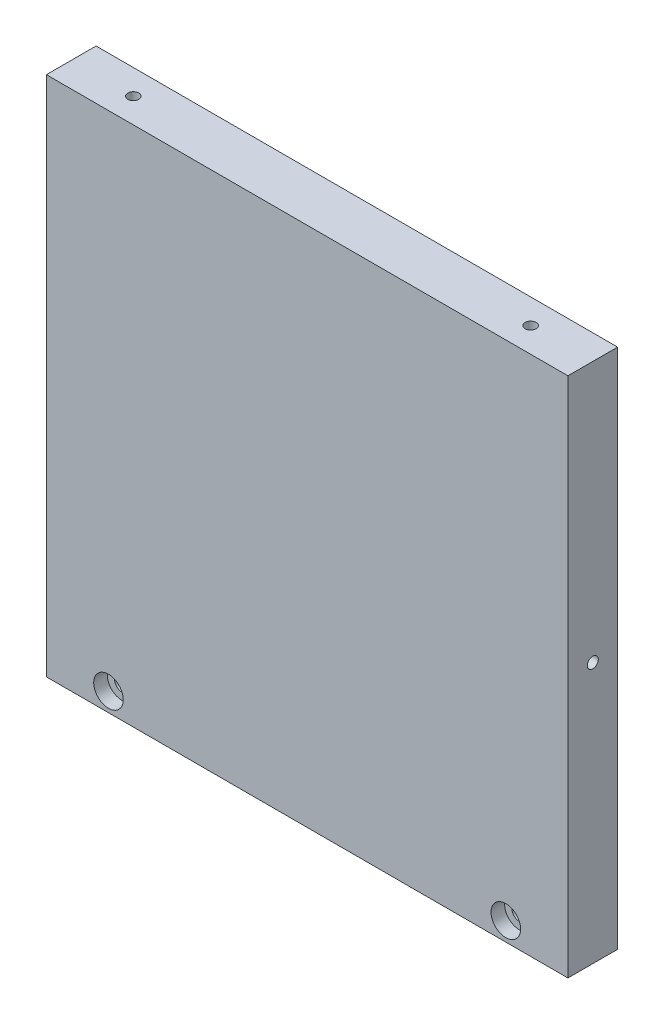
SolidWorks part; units mm, degrees
ref_plane "Front Plane" through (0, 0, 0) normal (0, 0, 1) x (1, 0, 0)
ref_plane "Top Plane" through (0, 0, 0) normal (0, 1, 0) x (1, 0, 0)
ref_plane "Right Plane" through (0, 0, 0) normal (1, 0, 0) x (0, 0, -1)
sketch "Sketch1" plane through (0, 0, 0) normal (0, 0, 1) x (1, 0, 0)
  line L1 (-42, 42) -> (42, 42)
  line L2 (-42, 42) -> (-42, -42)
  line L3 (-42, -42) -> (42, -42)
  line L4 (42, 42) -> (42, -42)
  line L5 (-42, 42) -> (42, -42) construction
  line L6 (-42, -42) -> (42, 42) construction
  point P0 (0, 0)
extrude "Boss-Extrude1" add sketch "Sketch1" along normal blind 8
sketch "Sketch2" plane through (0, 0, 8) normal (0, 0, 1) x (1, 0, 0)
  line L0 (-42, -42) -> (-42, -36) construction
  line L1 (-42, -36) -> (42, -36) construction
  line L2 (42, -42) -> (42, 42) construction
  line L3 (42, -36) -> (42, -42) construction
  line L4 (-42, -39) -> (-32, -39) construction
  line L5 (42, -39) -> (32, -39) construction
hole_wizard "CBORE for #2 Socket Head Cap Screw1" positions "3DSketch1" profile "Sketch3" counterbore size "#2" standard "ANSI Inch" end condition up to next
sketch3d "3DSketch1"
  point P0 (-32, -39, 8)
  point P3 (32, -39, 8)
sketch "Sketch3" plane through (-32, -39, 8) normal (1, 0, 0) x (0, -1, 0)
  line L0 (0, 0) -> (0, 8)
  line L1 (0, 8) -> (1.2192, 8)
  line L3 (1.2192, 8) -> (1.2192, 2.1844)
  line L4 (1.2192, 2.1844) -> (2.3812, 2.1844)
  line L5 (2.3812, 2.1844) -> (2.3812, 0)
  line L7 (2.3812, 0) -> (0, 0)
  line L11 (0, -6.35) -> (0, 107.95) construction
  dimension "Thru Hole Dia." = 2.4384
  dimension "Thru Hole Depth" = 8
  dimension "C'Bore Dia." = 4.7625
  dimension "C'Bore Depth" = 2.1844
sketch "Sketch4" plane through (42, 0, 0) normal (1, 0, 0) x (0, 0, -1)
  line L0 (-4, -42) -> (-4, 0) construction
  line L1 (-8, -42) -> (0, -42) construction
hole_wizard "#2-56 Tapped Hole1" positions "3DSketch2" profile "Sketch5" tap size "#2-56" standard "ANSI Inch"
sketch3d "3DSketch2"
  point P0 (42, 0, 4)
sketch "Sketch5" plane through (42, 0, 4) normal (0, 1, 0) x (0, 0, -1)
  line L0 (0, 0) -> (0, 12.5342)
  line L1 (0, 12.5342) -> (0.889, 12)
  line L2 (0.889, 12) -> (0.889, 0)
  line L5 (0.889, 0) -> (0, 0)
  line L10 (0, 12.5342) -> (-0.889, 12) construction
  line L11 (0, -6.35) -> (0, 107.95) construction
  dimension "Tap Drill Dia." = 1.778
  dimension "Tap Drill Depth" = 12
  dimension "Drill Angle" = 118
cosmetic thread "Hole Thread1" parameters "D1"=10, "D2"=2.1844
sketch "Sketch6" plane through (-42, 0, 0) normal (-1, 0, 0) x (0, 0, 1)
  line L0 (4, -42) -> (4, 0) construction
  line L1 (8, -42) -> (0, -42) construction
hole_wizard "#2-56 Tapped Hole2" positions "3DSketch3" profile "Sketch7" tap size "#2-56" standard "ANSI Inch"
sketch3d "3DSketch3"
  point P0 (-42, 0, 4)
sketch "Sketch7" plane through (-42, 0, 4) normal (0, 1, 0) x (0, 0, 1)
  line L0 (0, 0) -> (0, 12.5342)
  line L1 (0, 12.5342) -> (0.889, 12)
  line L2 (0.889, 12) -> (0.889, 0)
  line L5 (0.889, 0) -> (0, 0)
  line L10 (0, 12.5342) -> (-0.889, 12) construction
  line L11 (0, -6.35) -> (0, 107.95) construction
  dimension "Tap Drill Dia." = 1.778
  dimension "Tap Drill Depth" = 12
  dimension "Drill Angle" = 118
cosmetic thread "Hole Thread2" parameters "D1"=10, "D2"=2.1844
sketch "Sketch8" plane through (0, 42, 0) normal (0, 1, 0) x (1, 0, 0)
  line L0 (-42, -4) -> (-32, -4) construction
  line L1 (-42, -8) -> (-42, 0) construction
  line L2 (42, -4) -> (32, -4) construction
  line L3 (42, -8) -> (42, 0) construction
hole_wizard "#2-56 Tapped Hole3" positions "3DSketch4" profile "Sketch9" tap size "#2-56" standard "ANSI Inch"
sketch3d "3DSketch4"
  point P0 (-32, 42, 4)
  point P3 (32, 42, 4)
sketch "Sketch9" plane through (-32, 42, 4) normal (1, 0, 0) x (0, 0, 1)
  line L0 (0, 0) -> (0, 12.5342)
  line L1 (0, 12.5342) -> (0.889, 12)
  line L2 (0.889, 12) -> (0.889, 0)
  line L5 (0.889, 0) -> (0, 0)
  line L10 (0, 12.5342) -> (-0.889, 12) construction
  line L11 (0, -6.35) -> (0, 107.95) construction
  dimension "Tap Drill Dia." = 1.778
  dimension "Tap Drill Depth" = 12
  dimension "Drill Angle" = 118
cosmetic thread "Hole Thread3" parameters "D1"=10, "D2"=2.1844
cosmetic thread "Hole Thread4" parameters "D1"=10, "D2"=2.1844
